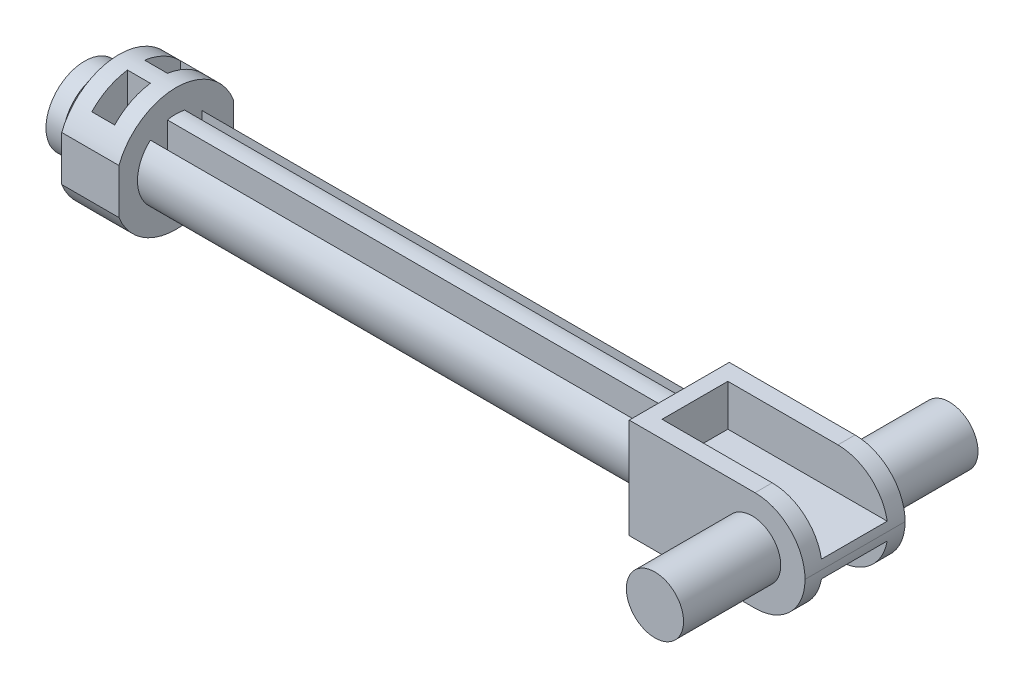
SolidWorks part; units mm, degrees
ref_plane "Front Plane" through (0, 0, 0) normal (0, 0, 1) x (1, 0, 0)
ref_plane "Top Plane" through (0, 0, 0) normal (0, 1, 0) x (1, 0, 0)
ref_plane "Right Plane" through (0, 0, 0) normal (1, 0, 0) x (0, 0, -1)
sketch "Sketch1" plane through (0, 0, 0) normal (0, 1, 0) x (1, 0, 0)
  line L1 (6.15, -3.5) -> (-6.15, -3.5)
  line L2 (6.15, -3.5) -> (6.15, 3.5)
  line L3 (6.15, 3.5) -> (-6.15, 3.5)
  line L4 (-6.15, -3.5) -> (-6.15, 3.5)
  line L5 (6.15, -3.5) -> (-6.15, 3.5) construction
  line L6 (6.15, 3.5) -> (-6.15, -3.5) construction
  point P0 (0, 0)
  dimension "D1" = 7
  dimension "D2" = 12.3
extrude "Boss-Extrude1" add sketch "Sketch1" along normal blind 7
sketch "Sketch2" plane through (0, 7, 0) normal (0, 1, 0) x (1, 0, 0)
  line L0 (6.15, -3.5) -> (6.15, 3.5) construction
  line L1 (6.15, -2.3) -> (-5.05, -2.3)
  line L2 (6.15, -2.3) -> (6.15, 2.3)
  line L3 (6.15, 2.3) -> (-5.05, 2.3)
  line L4 (-5.05, -2.3) -> (-5.05, 2.3)
  line L5 (-6.15, 3.5) -> (-6.15, -3.5) construction
  line L6 (6.15, 3.5) -> (-6.15, 3.5) construction
  line L7 (-6.15, -3.5) -> (6.15, -3.5) construction
  dimension "D1" = 1.1
  dimension "D2" = 1.2
  dimension "D3" = 1.2
extrude "Cut-Extrude1" cut sketch "Sketch2" against normal blind 2.9
ref_plane "Plane1" through (0, 3.5, 0) normal (0, 1, 0) x (1, 0, 0)
mirror "Mirror1" about plane through (0, 3.5, 0) normal (0, 1, 0) of "Cut-Extrude1"
sketch "Sketch4" plane through (0, 0, 3.5) normal (0, 0, 1) x (1, 0, 0)
  line L0 (0, 0) -> (0, 7.9416) construction
  line L1 (-7.0519, 3.5) -> (6.938, 3.5) construction
  line L3 (-6.15, 7) -> (-6.15, 0) construction
  circle A0 centre (2.45, 3.5) radius 2
  dimension "D1" = 4
  dimension "D2" = 8.6
extrude "Boss-Extrude2" add sketch "Sketch4" along normal blind 6.8
ref_plane "Plane2" through (0, 0, 0) normal (0, 0, 1) x (1, 0, 0)
mirror "Mirror2" about plane through (0, 0, 0) normal (0, 0, 1) of "Boss-Extrude2"
sketch "Sketch5" plane through (-6.15, 0, 0) normal (-1, 0, 0) x (0, 0, 1)
  line L0 (-3.5, 3.5) -> (49996.5, 3.5) construction
  line L1 (-3.5, 7) -> (-3.5, 0) construction
  line L2 (3.5, 1.5) -> (3.5, 5.5) construction
  line L3 (0, 7) -> (0, -49993) construction
  line L4 (-3.5, 7) -> (3.5, 7) construction
  circle A0 centre (0, 3.5) radius 2.7
  point P4 (-3.5, 3.5)
  point P7 (3.5, 3.5)
  point P12 (0, 7)
  dimension "D1" = 5.4
extrude "Boss-Extrude3" add sketch "Sketch5" along normal blind 35.2
sketch "Sketch6" plane through (-41.35, 0, 0) normal (-1, 0, 0) x (0, 0, 1)
  circle A0 centre (0, 3.5) radius 4.3
  dimension "D1" = 8.6
extrude "Boss-Extrude4" add sketch "Sketch6" along normal blind 4
sketch "Sketch7" plane through (0, 0, 0) normal (0, -1, 0) x (-1, 0, 0)
  line L0 (41.35, 0) -> (-49958.65, 0) construction
  line L1 (41.35, 4.3) -> (41.35, -4.3) construction
  line L2 (6.15, -2.7) -> (6.15, 2.7) construction
  line L3 (6.15, 3.5) -> (6.15, -3.5) construction
  line L4 (6.15, 0.6) -> (41.35, 0.6)
  line L5 (6.15, 0.6) -> (6.15, 1.8)
  line L6 (6.15, 1.8) -> (41.35, 1.8)
  line L7 (41.35, 0.6) -> (41.35, 1.8)
  point P4 (41.35, 0)
  point P7 (6.15, 0)
  dimension "D1" = 0.6
  dimension "D2" = 1.2
extrude "Cut-Extrude2" cut sketch "Sketch7" against normal blind 2.9
mirror "Mirror3" about plane through (0, 3.5, 0) normal (0, 1, 0) of "Cut-Extrude2"
mirror "Mirror4" about plane through (0, 0, 0) normal (0, 0, 1) of "Mirror3"
ref_plane "Plane3" through (0, 4.1, 0) normal (0, 1, 0) x (1, 0, 0)
sketch "Sketch9" plane through (0, 4.1, 0) normal (0, 1, 0) x (1, 0, 0)
  line L0 (-45.35, 0) -> (49954.65, 0) construction
  line L1 (-45.35, 4.3) -> (-45.35, -4.3) construction
  line L2 (-41.35, -4.3) -> (-41.35, 4.3) construction
  line L3 (-45.35, -4.3) -> (-41.35, -4.3) construction
  line L4 (-44.15, -0.6) -> (-42.55, -0.6)
  line L5 (-44.15, -0.6) -> (-44.15, -3.1)
  line L6 (-44.15, -3.1) -> (-42.55, -3.1)
  line L7 (-42.55, -0.6) -> (-42.55, -3.1)
  point P4 (-45.35, 0)
  point P7 (-41.35, 0)
  dimension "D1" = 1.2
  dimension "D2" = 1.2
  dimension "D3" = 0.6
  dimension "D4" = 1.2
extrude "Cut-Extrude3" cut sketch "Sketch9" along normal up to surface (3.6579 mm away) up to face at (-45.35, 3.5, 4.3)
mirror "Mirror5" about plane through (0, 3.5, 0) normal (0, 1, 0) of "Cut-Extrude3"
mirror "Mirror6" about plane through (0, 0, 0) normal (0, 0, 1) of "Mirror5"
sketch "Sketch10" plane through (-45.35, 0, 0) normal (-1, 0, 0) x (0, 0, 1)
  line L1 (2, 2.9) -> (-2, 2.9)
  line L2 (2, 2.9) -> (2, 4.1)
  line L3 (2, 4.1) -> (-2, 4.1)
  line L4 (-2, 2.9) -> (-2, 4.1)
  line L5 (2, 2.9) -> (-2, 4.1) construction
  line L6 (2, 4.1) -> (-2, 2.9) construction
  line L7 (-0.6, 1.5) -> (0.6, 1.5)
  line L8 (-0.6, 1.5) -> (-0.6, 5.5)
  line L9 (-0.6, 5.5) -> (0.6, 5.5)
  line L10 (0.6, 1.5) -> (0.6, 5.5)
  line L11 (-0.6, 1.5) -> (0.6, 5.5) construction
  line L12 (-0.6, 5.5) -> (0.6, 1.5) construction
  point P0 (0, 3.5)
  point P6 (0, 3.5)
  dimension "D1" = 1.2
  dimension "D2" = 4
extrude "Boss-Extrude5" add sketch "Sketch10" along normal blind 1.2 contours L10 L1 L2 L3 | L7 L10 L1 L8 | L1 L8 L3 L4 | L3 L10 L9 L8 | L1 L10 L3 L8 region at (-45.35, 3.5, 1.3) region at (-45.35, 2.2, 0) region at (-45.35, 3.5, 0) region at (-45.35, 3.5, -1.3) region at (-45.35, 4.8, 0)
sketch "Sketch11" plane through (-46.55, 0, 0) normal (-1, 0, 0) x (0, 0, 1)
  circle A0 centre (0, 3.5) radius 2.7
  dimension "D1" = 5.4
extrude "Boss-Extrude6" add sketch "Sketch11" along normal blind 1.2
sketch "Sketch12" plane through (-47.75, 0, 0) normal (-1, 0, 0) x (0, 0, 1)
  line L0 (-2, 2.9) -> (-2, 4.1) construction
  line L1 (2.7, 2.9) -> (-2.7, 2.9)
  line L2 (2.7, 2.9) -> (2.7, 4.1)
  line L3 (2.7, 4.1) -> (-2.7, 4.1)
  line L4 (-2.7, 2.9) -> (-2.7, 4.1)
  line L5 (2.7, 2.9) -> (-2.7, 4.1) construction
  line L6 (2.7, 4.1) -> (-2.7, 2.9) construction
  line L8 (0.6, 0.8) -> (-0.6, 0.8)
  line L9 (0.6, 0.8) -> (0.6, 6.2)
  line L10 (0.6, 6.2) -> (-0.6, 6.2)
  line L11 (-0.6, 0.8) -> (-0.6, 6.2)
  line L12 (0.6, 0.8) -> (-0.6, 6.2) construction
  line L13 (0.6, 6.2) -> (-0.6, 0.8) construction
  circle A0 centre (0, 3.5) radius 2.7 construction
  point P0 (0, 3.5)
  point P10 (0, 3.5)
  circle M9 centre (0, 3.5) radius 2.7
extrude "Boss-Extrude9" add sketch "Sketch12" along normal blind 0.8 contours L1 L11 L3 M9 | L11 L3 L9 M9 | L9 L1 L3 M9 | L11 L9 L1 M9 | L11 L1 L9 L3 region at (-47.75, 3.5, 1.6389) region at (-47.75, 1.8611, 0) region at (-47.75, 3.5, 0) region at (-47.75, 3.5, -1.6389) region at (-47.75, 5.1389, 0)
sketch "Sketch13" plane through (0, 0, 0) normal (0, 0, 1) x (1, 0, 0)
  line L0 (-48.75, 3.5) -> (-50.5061, 3.5) construction
  line L4 (-46.55, 6.2) -> (-48.55, 6.2) construction
  line L5 (-47.75, 6.1325) -> (-47.75, 4.1) construction
  line L6 (-47.75, 6.2) -> (-50.2644, 6.8683)
  line L7 (-50.2644, 6.8683) -> (-50.6913, 5.2197)
  line L8 (-50.6913, 5.2197) -> (-49.9248, 3.5)
  line L9 (-49.9248, 3.5) -> (-48.55, 3.5)
  line L10 (-48.55, 4.1) -> (-48.55, 2.9) construction
  arc A1 (-48.55, 3.5) -> (-47.75, 6.2) centre (-44.3066, 3.7112) cw
  dimension "D1" = 0
revolve "Cut-Revolve6" cut sketch "Sketch13" angle 360 about L0
fillet "Fillet3" radius 3.5 2 edges at (6.15, 0, 2.9) (6.15, 7, 2.9)
sketch "Sketch14" plane through (-45.35, 0, 0) normal (-1, 0, 0) x (0, 0, 1)
  line L1 (4, -2.5) -> (-4, -2.5)
  line L2 (4, -2.5) -> (4, 9.5)
  line L3 (4, 9.5) -> (-4, 9.5) construction
  line L4 (-4, -2.5) -> (-4, 9.5)
  line L5 (4, -2.5) -> (-4, 9.5) construction
  line L6 (4, 9.5) -> (-4, -2.5) construction
  line L7 (-4, 9.5) -> (-5, 9.5)
  line L8 (-4, 9.5) -> (-4, -2.5)
  line L9 (-4, -2.5) -> (-5, -2.5)
  line L10 (-5, 9.5) -> (-5, -2.5)
  line L11 (4, -2.5) -> (5, -2.5)
  line L12 (4, -2.5) -> (4, 9.5)
  line L13 (4, 9.5) -> (5, 9.5)
  line L14 (5, -2.5) -> (5, 9.5)
  point P0 (0, 3.5)
  circle M25 centre (0, 3.5) radius 4.3
  dimension "D1" = 8
  dimension "D2" = 12
  dimension "D3" = 1
extrude "Cut-Extrude8" cut sketch "Sketch14" against normal blind 5 contours L7 L10 L9 L4 M25 | L11 L14 L13 L2 M25 | L8 L7 L10 L9 | L12 L11 L14 L13 region at (-45.35, 3.5, 4.5212) region at (-45.35, 3.5, -4.5212)
